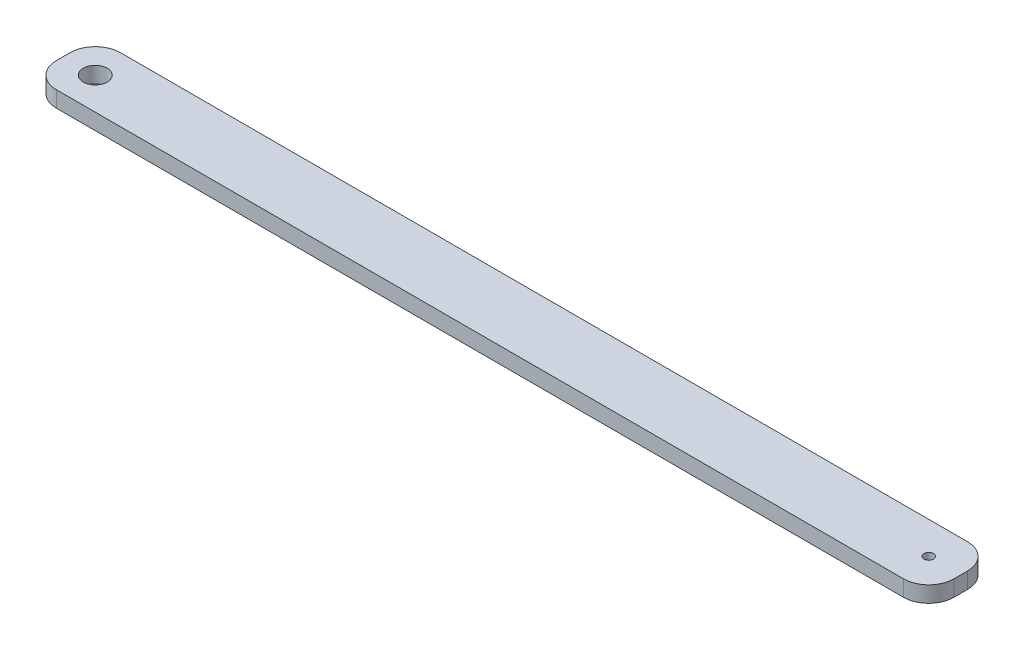
SolidWorks part; units mm, degrees
ref_plane "Front Plane" through (0, 0, 0) normal (0, 0, 1) x (1, 0, 0)
ref_plane "Top Plane" through (0, 0, 0) normal (0, 1, 0) x (1, 0, 0)
ref_plane "Right Plane" through (0, 0, 0) normal (1, 0, 0) x (0, 0, -1)
sketch "Sketch1" plane through (0, 0, 0) normal (0, 1, 0) x (1, 0, 0)
  line L1 (-177.8, -12.7) -> (177.8, -12.7)
  line L2 (-177.8, -12.7) -> (-177.8, 12.7)
  line L3 (-177.8, 12.7) -> (177.8, 12.7)
  line L4 (177.8, -12.7) -> (177.8, 12.7)
  line L5 (-177.8, -12.7) -> (177.8, 12.7) construction
  line L6 (-177.8, 12.7) -> (177.8, -12.7) construction
  point P0 (0, 0)
  dimension "D1" = 25.4
  dimension "D2" = 355.6
extrude "Boss-Extrude1" add sketch "Sketch1" along normal mid plane 6.35
fillet "Fillet1" radius 10 4 edges at (177.8, 0, -12.7) (177.8, 0, 12.7) (-177.8, 0, -12.7) (-177.8, 0, 12.7)
sketch "Sketch2" plane through (0, 3.175, 0) normal (0, 1, 0) x (1, 0, 0)
  line L0 (0, -36.7292) -> (0, 36.7292) construction
  line L1 (165.1, 0) -> (-165.1, 0) construction
  line L2 (-177.8, 2.7) -> (-177.8, -2.7) construction
  point P7 (0, 0)
  point P8 (105.5002, 0)
  point P10 (0, 0)
  point P11 (0, 0)
  dimension "D1" = 12.7
hole_wizard "#10-24 Tapped Hole1" positions "Sketch5" profile "Sketch7" tap size "#10-24" standard "ANSI Inch" end condition through all
sketch "Sketch5" plane through (0, 3.175, 0) normal (0, 1, 0) x (1, 0, 0)
  point P0 (165.1, 0)
sketch "Sketch7" plane through (165.1, 3.175, 0) normal (1, 0, 0) x (0, 0, 1)
  line L0 (0, 0) -> (0, 6.35)
  line L1 (0, 6.35) -> (1.8986, 6.35)
  line L2 (1.8986, 6.35) -> (1.8986, 0)
  line L5 (1.8986, 0) -> (0, 0)
  line L11 (0, -6.35) -> (0, 107.95) construction
  dimension "Thru Tap Drill Dia." = 3.7973
  dimension "Thru Tap Drill Depth" = 6.35
cosmetic thread "Hole Thread1" parameters "D2"=4.826
sketch "Sketch8" plane through (0, 3.175, 0) normal (0, 1, 0) x (1, 0, 0)
  circle A0 centre (-165.1, 0) radius 4.7625
  dimension "D1" = 9.525
extrude "Cut-Extrude1" cut sketch "Sketch8" against normal through all
